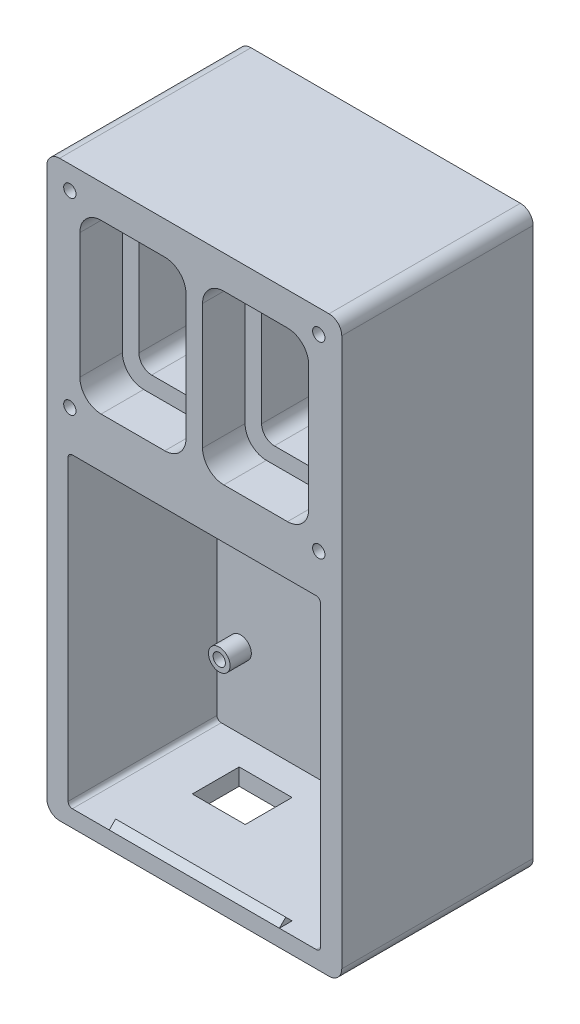
SolidWorks part; units mm, degrees
ref_plane "Front Plane" through (0, 0, 0) normal (0, 0, 1) x (1, 0, 0)
ref_plane "Top Plane" through (0, 0, 0) normal (0, 1, 0) x (1, 0, 0)
ref_plane "Right Plane" through (0, 0, 0) normal (1, 0, 0) x (0, 0, -1)
sketch "Sketch1" plane through (0, 0, 0) normal (0, 0, 1) x (1, 0, 0)
  line L0 (-8.8291, 40.628) -> (-20.0291, 40.628) construction
  line L1 (-34.67, 67.4487) -> (34.67, 67.4487)
  line L2 (-34.67, 67.4487) -> (-34.67, -67.4487)
  line L3 (-34.67, -67.4487) -> (34.67, -67.4487)
  line L4 (34.67, 67.4487) -> (34.67, -67.4487)
  line L5 (-20.0233, 52.802) -> (-8.8233, 52.802) construction
  line L6 (-20.0233, 52.802) -> (-20.0233, 39.128) construction
  line L7 (-20.0233, 39.128) -> (-8.8233, 39.128) construction
  line L8 (-8.8233, 52.802) -> (-8.8233, 39.128) construction
  line L9 (8.8233, 52.802) -> (20.0233, 52.802) construction
  line L10 (8.8233, 52.802) -> (8.8233, 39.128) construction
  line L11 (8.8233, 39.128) -> (20.0233, 39.128) construction
  line L12 (20.0233, 52.802) -> (20.0233, 39.128) construction
  line L13 (-8.8291, 40.628) -> (-8.8291, 54.302) construction
  line L14 (-26.67, 7.4813) -> (26.67, 7.4813) construction
  line L15 (-26.67, 7.4813) -> (26.67, 7.4813) construction
  line L16 (-26.67, 7.4813) -> (-26.67, -67.4487) construction
  line L17 (-26.67, -67.4487) -> (26.67, -67.4487) construction
  line L18 (26.67, 7.4813) -> (26.67, -67.4487) construction
  line L19 (26.67, 7.4813) -> (26.67, -67.4487) construction
  line L20 (-23.0233, 55.802) -> (-34.67, 55.802) construction
  line L29 (-5.8233, 55.802) -> (-5.8233, 24.128)
  line L30 (-23.0233, 24.128) -> (-5.8233, 24.128)
  line L31 (-23.0233, 55.802) -> (-23.0233, 24.128)
  line L32 (-23.0233, 55.802) -> (-5.8233, 55.802)
  line L33 (5.8233, 24.128) -> (23.0233, 24.128)
  line L34 (23.0233, 55.802) -> (23.0233, 24.128)
  line L35 (5.8233, 55.802) -> (23.0233, 55.802)
  line L36 (5.8233, 55.802) -> (5.8233, 24.128)
  line L37 (29.67, -67.4487) -> (29.67, 12.4813)
  line L38 (29.67, 12.4813) -> (-29.67, 12.4813)
  line L39 (-29.67, 12.4813) -> (-29.67, -67.4487)
  line L40 (-14.4233, 24.128) -> (-14.4233, 12.4813) construction
  line L41 (-14.4233, 55.802) -> (-14.4233, 67.4487) construction
  line L42 (-5.8233, 55.802) -> (5.8233, 55.802) construction
  line L43 (-23.0233, 24.128) -> (-34.67, 24.128) construction
  line L44 (23.0233, 55.802) -> (34.67, 55.802) construction
  point P4 (-34.67, 0)
  point P5 (0, 67.4487)
  point P31 (0, -67.4487)
  point P32 (0, -67.4487)
  point P46 (0, 12.4813)
  point P53 (-14.4233, 52.802)
  point P61 (14.4233, 52.802)
  point P62 (14.4233, 55.802)
  dimension "D1" = 3
  dimension "D2" = 3
  dimension "D3" = 3
  dimension "D4" = 5
  dimension "D5" = 5
  dimension "D6" = 15
extrude "Boss-Extrude1" add sketch "Sketch1" along normal blind 10 contours L39 L38 L37 L3 L4 L1 L2 L36 L35 L34 L33 L31 L32 L29 L30 | L38 L39 L3 L37 | L35 L36 L33 L34 | L32 L31 L30 L29 region at (0, 24.6542, 0) region at (0, -27.4837, 0) region at (-14.4233, 39.965, 0) region at (14.4233, 39.965, 0)
extrude "Boss-Extrude2" add sketch "Sketch1<3>" along normal blind 35 contours L39 L38 L37 L3 L4 L1 L2 L36 L35 L34 L33 L31 L32 L29 L30 region at (0, 24.6542, 0)
sketch "Sketch1<3>" plane through (0, 0, 0) normal (0, 0, 1) x (1, 0, 0) same geometry as "Sketch1"
sketch "Sketch2" plane through (0, -67.4487, 0) normal (0, -1, 0) x (1, 0, 0)
  line L1 (-29.67, 10) -> (29.67, 10)
  line L2 (-29.67, 10) -> (-29.67, 35)
  line L3 (-29.67, 35) -> (29.67, 35)
  line L4 (29.67, 10) -> (29.67, 35)
  line L5 (-17.57, 27.9) -> (-5.13, 27.9)
  line L6 (-17.57, 27.9) -> (-17.57, 16.88)
  line L7 (-17.57, 16.88) -> (-5.13, 16.88)
  line L8 (-5.13, 27.9) -> (-5.13, 16.88)
  line L9 (-5.79, 27.7) -> (-16.91, 27.7) construction
  line L10 (-17.37, 27.14) -> (-17.37, 17.49) construction
  line L11 (-5.33, 17.49) -> (-5.33, 27.14) construction
  line L12 (-17.37, 17.08) -> (-5.33, 17.08) construction
  dimension "D1" = 0.2
  dimension "D2" = 0.2
  dimension "D3" = 0.2
  dimension "D4" = 0.2
extrude "Boss-Extrude3" add sketch "Sketch2" against normal offset from surface (3.945 mm away) 0.5
fillet "Fillet1" radius 3 4 edges at (34.67, 67.4487, 17.5) (34.67, -67.4487, 17.5) (-34.67, -67.4487, 17.5) (-34.67, 67.4487, 17.5)
fillet "Fillet2" radius 3 8 edges at (5.8233, 24.128, 22.5) (5.8233, 55.802, 22.5) (23.0233, 55.802, 22.5) (-5.8233, 55.802, 22.5) (23.0233, 24.128, 22.5) (-5.8233, 24.128, 22.5) (-23.0233, 55.802, 22.5) (-23.0233, 24.128, 22.5)
fillet "Fillet3" radius 1 4 edges at (29.67, 12.4813, 22.5) (29.67, -63.5037, 22.5) (-29.67, -63.5037, 22.5) (-29.67, 12.4813, 22.5)
sketch "Sketch4" plane through (0, 12.4813, 0) normal (0, -1, 0) x (-1, 0, 0)
  line L0 (18.6291, -33.14) -> (10.2291, -33.14) construction
  line L1 (11.7541, -26.23) -> (11.7541, -31.27) construction
  line L2 (11.7541, -26.23) -> (11.7541, -31.27) construction
  line L3 (14.4291, -31.2878) -> (15.8943, -28.75) construction
  line L4 (15.8943, -28.75) -> (14.4291, -26.2122) construction
  line L5 (14.4291, -26.2122) -> (12.9639, -28.75) construction
  line L6 (12.9639, -28.75) -> (14.4291, -31.2878) construction
  line L7 (13.8517, -26.2122) -> (12.8196, -28)
  line L8 (12.8196, -29.5) -> (13.8517, -31.2878)
  line L9 (15.0064, -31.2878) -> (16.0386, -29.5)
  line L10 (16.0386, -28) -> (15.0064, -26.2122)
  line L11 (14.4291, -25.2122) -> (12.3865, -28.75) construction
  line L12 (12.3865, -28.75) -> (14.4291, -32.2878) construction
  line L13 (14.4291, -32.2878) -> (16.4716, -28.75) construction
  line L14 (16.4716, -28.75) -> (14.4291, -25.2122) construction
  line L15 (15.0064, -31.2878) -> (13.8517, -31.2878)
  line L16 (15.0064, -26.2122) -> (13.8517, -26.2122)
  circle A0 centre (14.4291, -29.9278) radius 0.68 construction
  circle A1 centre (15.1091, -28.75) radius 0.68 construction
  circle A2 centre (13.7491, -28.75) radius 0.68 construction
  circle A3 centre (14.4291, -27.5722) radius 0.68 construction
  circle A4 centre (10.2291, -33.14) radius 0.68 construction
  circle A5 centre (18.6291, -33.14) radius 0.68 construction
  arc A6 (12.8196, -28) -> (12.8196, -29.5) centre (14.1186, -28.75) ccw
  arc A7 (16.0386, -29.5) -> (16.0386, -28) centre (14.7396, -28.75) ccw
  point P17 (14.4291, -33.14)
  point P32 (11.7541, -28.75)
  dimension "D1" = 0.5
  dimension "D2" = 1.5
extrude "Cut-Extrude1" cut sketch "Sketch4" against normal up to next
mirror "Mirror1" about plane through (0, 0, 0) normal (1, 0, 0) of "Cut-Extrude1"
sketch "Sketch5" plane through (0, 0, 35) normal (0, 0, 1) x (1, 0, 0)
  line L0 (-5.8233, 39.965) -> (-1.9411, 39.965) construction
  line L1 (-21.9056, 59.6842) -> (-6.9411, 59.6842)
  line L2 (-26.9056, 54.6842) -> (-26.9056, 25.2458)
  line L3 (-21.9056, 20.2458) -> (-6.9411, 20.2458)
  line L4 (-1.9411, 54.6842) -> (-1.9411, 25.2458)
  line L5 (6.9411, 59.6842) -> (21.9056, 59.6842)
  line L6 (1.9411, 54.6842) -> (1.9411, 25.2458)
  line L7 (6.9411, 20.2458) -> (21.9056, 20.2458)
  line L8 (26.9056, 54.6842) -> (26.9056, 25.2458)
  line L9 (-5.8233, 52.802) -> (-5.8233, 27.128) construction
  line L10 (-1.9411, 39.965) -> (1.9411, 39.965) construction
  line L11 (1.9411, 39.965) -> (5.8233, 39.965) construction
  line L12 (5.8233, 52.802) -> (5.8233, 27.128) construction
  line L13 (23.0233, 39.965) -> (26.9056, 39.965) construction
  line L14 (23.0233, 52.802) -> (23.0233, 27.128) construction
  line L15 (-23.0233, 39.965) -> (-26.9056, 39.965) construction
  line L16 (-23.0233, 52.802) -> (-23.0233, 27.128) construction
  line L17 (14.4233, 55.802) -> (14.4233, 59.6842) construction
  line L18 (8.8233, 55.802) -> (20.0233, 55.802) construction
  line L19 (-31.67, -67.4487) -> (31.67, -67.4487) construction
  line L20 (-31.67, -67.4487) -> (31.67, -67.4487)
  line L25 (29.67, -62.5037) -> (29.67, 11.4813)
  line L26 (28.67, 12.4813) -> (-28.67, 12.4813)
  line L27 (-29.67, 11.4813) -> (-29.67, -62.5037)
  line L28 (-28.67, -63.5037) -> (28.67, -63.5037)
  line L29 (29.67, -62.5037) -> (29.67, 11.4813)
  line L30 (28.67, 12.4813) -> (-28.67, 12.4813)
  line L35 (34.67, -64.4487) -> (34.67, 64.4487)
  line L36 (31.67, 67.4487) -> (-31.67, 67.4487)
  line L37 (-34.67, 64.4487) -> (-34.67, -64.4487)
  line L38 (-31.67, -67.4487) -> (31.67, -67.4487)
  line L39 (34.67, -64.4487) -> (34.67, 64.4487)
  line L40 (31.67, 67.4487) -> (-31.67, 67.4487)
  line L41 (-34.67, 64.4487) -> (-34.67, -64.4487)
  line L43 (-29.67, 11.4813) -> (-29.67, -62.5037)
  line L44 (-28.67, -63.5037) -> (28.67, -63.5037)
  line L49 (29.67, -62.5037) -> (29.67, 11.4813)
  line L50 (28.67, 12.4813) -> (-28.67, 12.4813)
  line L51 (-29.67, 11.4813) -> (-29.67, -62.5037)
  line L52 (-28.67, -63.5037) -> (28.67, -63.5037)
  arc A0 (21.9056, 59.6842) -> (26.9056, 54.6842) centre (21.9056, 54.6842) cw
  arc A1 (6.9411, 59.6842) -> (1.9411, 54.6842) centre (6.9411, 54.6842) ccw
  arc A2 (21.9056, 20.2458) -> (26.9056, 25.2458) centre (21.9056, 25.2458) ccw
  arc A3 (1.9411, 25.2458) -> (6.9411, 20.2458) centre (6.9411, 25.2458) ccw
  arc A4 (-6.9411, 20.2458) -> (-1.9411, 25.2458) centre (-6.9411, 25.2458) ccw
  arc A5 (-26.9056, 25.2458) -> (-21.9056, 20.2458) centre (-21.9056, 25.2458) ccw
  arc A6 (-6.9411, 59.6842) -> (-1.9411, 54.6842) centre (-6.9411, 54.6842) cw
  arc A7 (-21.9056, 59.6842) -> (-26.9056, 54.6842) centre (-21.9056, 54.6842) ccw
  arc A8 (31.67, -67.4487) -> (34.67, -64.4487) centre (31.67, -64.4487) ccw construction
  arc A9 (-34.67, -64.4487) -> (-31.67, -67.4487) centre (-31.67, -64.4487) ccw construction
  arc A10 (31.67, -67.4487) -> (34.67, -64.4487) centre (31.67, -64.4487) ccw
  arc A11 (-34.67, -64.4487) -> (-31.67, -67.4487) centre (-31.67, -64.4487) ccw
  arc A14 (29.67, 11.4813) -> (28.67, 12.4813) centre (28.67, 11.4813) ccw
  arc A15 (-28.67, 12.4813) -> (-29.67, 11.4813) centre (-28.67, 11.4813) ccw
  arc A16 (-29.67, -62.5037) -> (-28.67, -63.5037) centre (-28.67, -62.5037) ccw
  arc A17 (28.67, -63.5037) -> (29.67, -62.5037) centre (28.67, -62.5037) ccw
  arc A18 (29.67, 11.4813) -> (28.67, 12.4813) centre (28.67, 11.4813) ccw
  arc A19 (-28.67, 12.4813) -> (-29.67, 11.4813) centre (-28.67, 11.4813) ccw
  arc A24 (34.67, 64.4487) -> (31.67, 67.4487) centre (31.67, 64.4487) ccw
  arc A25 (-31.67, 67.4487) -> (-34.67, 64.4487) centre (-31.67, 64.4487) ccw
  arc A26 (-34.67, -64.4487) -> (-31.67, -67.4487) centre (-31.67, -64.4487) ccw
  arc A27 (31.67, -67.4487) -> (34.67, -64.4487) centre (31.67, -64.4487) ccw
  arc A28 (34.67, 64.4487) -> (31.67, 67.4487) centre (31.67, 64.4487) ccw
  arc A29 (-31.67, 67.4487) -> (-34.67, 64.4487) centre (-31.67, 64.4487) ccw
  arc A32 (-29.67, -62.5037) -> (-28.67, -63.5037) centre (-28.67, -62.5037) ccw
  arc A33 (28.67, -63.5037) -> (29.67, -62.5037) centre (28.67, -62.5037) ccw
  arc A38 (29.67, 11.4813) -> (28.67, 12.4813) centre (28.67, 11.4813) ccw
  arc A39 (-28.67, 12.4813) -> (-29.67, 11.4813) centre (-28.67, 11.4813) ccw
  arc A40 (-29.67, -62.5037) -> (-28.67, -63.5037) centre (-28.67, -62.5037) ccw
  arc A41 (28.67, -63.5037) -> (29.67, -62.5037) centre (28.67, -62.5037) ccw
  line M29 (34.67, -64.4487) -> (34.67, 64.4487)
  arc M30 (34.67, 64.4487) -> (31.67, 67.4487) centre (31.67, 64.4487) ccw
  line M31 (31.67, 67.4487) -> (-31.67, 67.4487)
  arc M32 (-31.67, 67.4487) -> (-34.67, 64.4487) centre (-31.67, 64.4487) ccw
  line M33 (-34.67, 64.4487) -> (-34.67, -64.4487)
  arc M34 (-34.67, -64.4487) -> (-31.67, -67.4487) centre (-31.67, -64.4487) ccw
  line M35 (-31.67, -67.4487) -> (31.67, -67.4487)
  arc M36 (31.67, -67.4487) -> (34.67, -64.4487) centre (31.67, -64.4487) ccw
  line M37 (-29.67, -62.5037) -> (-29.67, 11.4813)
  arc M38 (-29.67, 11.4813) -> (-28.67, 12.4813) centre (-28.67, 11.4813) cw
  line M39 (-28.67, 12.4813) -> (28.67, 12.4813)
  arc M40 (28.67, 12.4813) -> (29.67, 11.4813) centre (28.67, 11.4813) cw
  line M41 (29.67, 11.4813) -> (29.67, -62.5037)
  arc M42 (29.67, -62.5037) -> (28.67, -63.5037) centre (28.67, -62.5037) cw
  line M43 (28.67, -63.5037) -> (-28.67, -63.5037)
  arc M44 (-28.67, -63.5037) -> (-29.67, -62.5037) centre (-28.67, -62.5037) cw
  dimension "D1" = 5
  dimension "D2" = 0
  dimension "D3" = 0
extrude "Boss-Extrude4" add sketch "Sketch5" along normal blind 10 contours A7 L1 A6 L4 A4 L3 A5 L2 A3 L6 A1 L5 A0 L8 A2 L7 M36 M29 M30 M31 M32 M33 M34 M35 M44 M37 M38 M39 M40 M41 M42 M43 region at (0, 13.0595, 35)
sketch "Sketch7" plane through (0, 0, 45) normal (0, 0, 1) x (1, 0, 0)
  line L0 (25.4411, 58.2198) -> (29.2638, 62.0425) construction
  line L1 (-28.67, 12.4813) -> (28.67, 12.4813) construction
  line L2 (-34.67, 64.4487) -> (-34.67, -64.4487) construction
  line L3 (29.2638, 62.0425) -> (29.2638, 67.4487) construction
  line L4 (34.67, -64.4487) -> (34.67, 64.4487) construction
  line L5 (31.67, 67.4487) -> (-31.67, 67.4487) construction
  line L9 (29.2638, 62.0425) -> (34.67, 62.0425) construction
  line L13 (-25.4411, 21.7102) -> (-29.2638, 17.8875) construction
  line L14 (-29.2638, 17.8875) -> (-34.67, 17.8875) construction
  line L16 (-29.2638, 17.8875) -> (-29.2638, 12.4813) construction
  circle A0 centre (-29.2638, 17.8875) radius 1.45
  circle A1 centre (-29.2638, 62.0425) radius 1.45
  circle A2 centre (29.2638, 62.0425) radius 1.45
  circle A3 centre (29.2638, 17.8875) radius 1.45
  arc A6 (-26.9056, 25.2458) -> (-21.9056, 20.2458) centre (-21.9056, 25.2458) ccw construction
  arc A7 (26.9056, 54.6842) -> (21.9056, 59.6842) centre (21.9056, 54.6842) ccw construction
  dimension "D1" = 2.9
extrude "Cut-Extrude2" cut sketch "Sketch7" against normal blind 15
sketch "Sketch9" plane through (0, 0, 10) normal (0, 0, 1) x (1, 0, 0)
  line L1 (-26.67, 4.9413) -> (-26.67, -61.0987) construction
  circle A0 centre (-24.13, -45.8587) radius 1.45
  circle A1 centre (-8.89, 4.9413) radius 1.45
  circle A2 centre (19.05, 4.9413) radius 1.45
  circle A3 centre (24.13, -47.1287) radius 1.45
  circle A4 centre (19.05, 4.9413) radius 4.15
  circle A5 centre (-8.89, 4.9413) radius 4.15
  circle A6 centre (-24.13, -45.8587) radius 2.54
  circle A7 centre (24.13, -47.1287) radius 2.775
  dimension "D1" = 2.9
  dimension "D2" = 8.3
  dimension "D3" = 5.55
extrude "Boss-Extrude7" add sketch "Sketch9" along normal up to surface (5 mm away)
sketch "Sketch10" plane through (0, 0, 10) normal (0, 0, 1) x (1, 0, 0)
  circle A0 centre (24.13, -47.1287) radius 1.45 construction
  circle A1 centre (19.05, 4.9413) radius 1.45 construction
  circle A2 centre (-8.89, 4.9413) radius 1.45 construction
  circle A3 centre (-24.13, -45.8587) radius 1.45 construction
  circle A4 centre (24.13, -47.1287) radius 1.45
  circle A5 centre (19.05, 4.9413) radius 1.45
  circle A6 centre (-8.89, 4.9413) radius 1.45
  circle A7 centre (-24.13, -45.8587) radius 1.45
extrude "Cut-Extrude3" cut sketch "Sketch10" against normal offset from surface (1.35 mm away) 8
sketch "Sketch11" plane through (0, 0, 10) normal (0, 0, 1) x (1, 0, 0)
  line L0 (-20.0233, 55.802) -> (-8.8233, 55.802) construction
  line L1 (-20.0233, 55.802) -> (-8.8233, 55.802)
  line L2 (-23.0233, 45.959) -> (-5.8233, 45.959)
  line L3 (-23.0233, 52.802) -> (-23.0233, 27.128) construction
  line L4 (-5.8233, 52.802) -> (-5.8233, 27.128) construction
  line L5 (-14.4233, 48.74) -> (-14.4233, 54.302) construction
  line L6 (-28.67, 12.4813) -> (28.67, 12.4813) construction
  line L7 (-17.1041, 43.178) -> (-14.5541, 43.178) construction
  line L8 (-14.4233, 48.74) -> (-14.4233, 43.178) construction
  line L9 (-9.1983, 54.302) -> (-19.6483, 54.302) construction
  line L10 (-23.0233, 52.802) -> (-23.0233, 45.959)
  line L11 (-5.8233, 45.959) -> (-5.8233, 52.802)
  line L12 (0, 67.4487) -> (0, 12.4813) construction
  line L15 (31.67, 67.4487) -> (-31.67, 67.4487) construction
  line L17 (5.8233, 45.959) -> (5.8233, 52.802)
  line L18 (23.0233, 52.802) -> (23.0233, 45.959)
  line L19 (23.0233, 45.959) -> (5.8233, 45.959)
  line L20 (20.0233, 55.802) -> (8.8233, 55.802)
  circle A0 centre (-17.1983, 51.512) radius 1.2
  circle A1 centre (11.6483, 51.512) radius 1.2
  arc A2 (-5.8233, 52.802) -> (-8.8233, 55.802) centre (-8.8233, 52.802) ccw construction
  arc A3 (-20.0233, 55.802) -> (-23.0233, 52.802) centre (-20.0233, 52.802) ccw construction
  arc A4 (-5.8233, 52.802) -> (-8.8233, 55.802) centre (-8.8233, 52.802) ccw
  arc A5 (-20.0233, 55.802) -> (-23.0233, 52.802) centre (-20.0233, 52.802) ccw
  arc A6 (20.0233, 55.802) -> (23.0233, 52.802) centre (20.0233, 52.802) cw
  arc A7 (5.8233, 52.802) -> (8.8233, 55.802) centre (8.8233, 52.802) cw
  point P18 (-14.4233, 45.959)
  dimension "D1" = 2.4
extrude "Boss-Extrude8" add sketch "Sketch11" along normal up to surface (3 mm away)
sketch "Sketch12" plane through (0, 0, 10) normal (0, 0, 1) x (1, 0, 0)
  circle A1 centre (-17.1983, 51.512) radius 1.2
  circle A2 centre (-17.1983, 51.512) radius 1.2
  circle A3 centre (11.6483, 51.512) radius 1.2
  circle A4 centre (11.6483, 51.512) radius 1.2
  dimension "D1" = 0
  dimension "D2" = 0
extrude "Cut-Extrude5" cut sketch "Sketch12" against normal offset from surface (1.24 mm away) 6
sketch "Sketch13" plane through (-29.67, 0, 0) normal (1, 0, 0) x (0, 0, -1)
  line L0 (-45, -63.5037) -> (-45, -67.4487) construction
  line L3 (-45, -62.5037) -> (-45, 11.4813) construction
  line L4 (-45, 8.5363) -> (-40, 8.5363)
  line L5 (-45, 8.5363) -> (-45, 12.4813)
  line L6 (-45, 12.4813) -> (-40, 12.4813)
  line L7 (-40, 8.5363) -> (-40, 12.4813) construction
  line L9 (-40, 8.5363) -> (-36.055, 12.4813)
  line L10 (-36.055, 12.4813) -> (-40, 12.4813)
  dimension "D1" = 5
extrude "Boss-Extrude9" add sketch "Sketch13" along normal up to next
fillet "Fillet4" radius 1 8 edges at (0, 12.4813, 36.055) (29.3771, 12.1884, 36.3479) (-29.3771, 12.1884, 36.3479) (29.67, 10.0088, 38.5275) (-29.67, 10.0088, 38.5275) (0, 8.5363, 40) (29.67, 8.5363, 42.5) (-29.67, 8.5363, 42.5)
sketch "Sketch14" plane through (0, 0, 0) normal (1, 0, 0) x (0, 0, -1)
  line L0 (-45, 8.5363) -> (-43.5, 7.0363)
  line L1 (-43.5, 7.0363) -> (-42, 8.5363)
  line L2 (-42, 8.5363) -> (-45, 8.5363)
  line L3 (-43.5, 7.0363) -> (-43.5, 8.5363) construction
  line L4 (-10, -62.5037) -> (-10, 11.4813) construction
  line L5 (-45, -27.4837) -> (-10, -27.4837) construction
  line L6 (-45, -62.5037) -> (-45, 7.5363) construction
  line L7 (-42, -63.5037) -> (-45, -63.5037)
  line L8 (-43.5, -62.0037) -> (-42, -63.5037)
  line L9 (-45, -63.5037) -> (-43.5, -62.0037)
  dimension "D1" = 3
extrude "Boss-Extrude10" add sketch "Sketch14" along normal mid plane 40
sketch "Sketch15" plane through (0, 12.4813, 0) normal (0, -1, 0) x (1, 0, 0)
  line L0 (0, 10) -> (0, 45) construction
  line L1 (-28.67, 10) -> (28.67, 10) construction
  line L2 (20, 45) -> (-20, 45) construction
  point P0 (-14.4291, 29.9278)
  point P2 (-13.7491, 28.75)
  point P4 (-15.1091, 28.75)
  point P6 (-14.4291, 27.5722)
  point P16 (14.4291, 29.9278)
  point P17 (15.1091, 28.75)
  point P18 (13.7491, 28.75)
  point P19 (14.4291, 27.5722)
sketch "Sketch16" plane through (0, 24.128, 0) normal (0, 1, 0) x (1, 0, 0)
  point P0 (-15.1091, -28.75)
  point P2 (-14.4291, -29.9278)
  point P4 (-13.7491, -28.75)
  point P6 (-14.4291, -27.5722)
  point P8 (13.7491, -28.75)
  point P10 (14.4291, -27.5722)
  point P12 (14.4291, -29.9278)
  point P14 (15.1091, -28.75)
ref_plane "Plane1" through (0, 18.3047, 0) normal (0, 1, 0) x (1, 0, 0)
sketch "Sketch17" plane through (0, 18.3047, 0) normal (0, 1, 0) x (1, 0, 0)
  point P0 (-14.4291, -29.9278)
  point P2 (-13.7491, -28.75)
  point P4 (-15.1091, -28.75)
  point P6 (-14.4291, -27.5722)
  point P8 (13.7491, -28.75)
  point P10 (14.4291, -29.9278)
  point P12 (15.1091, -28.75)
  point P14 (14.4291, -27.5722)
